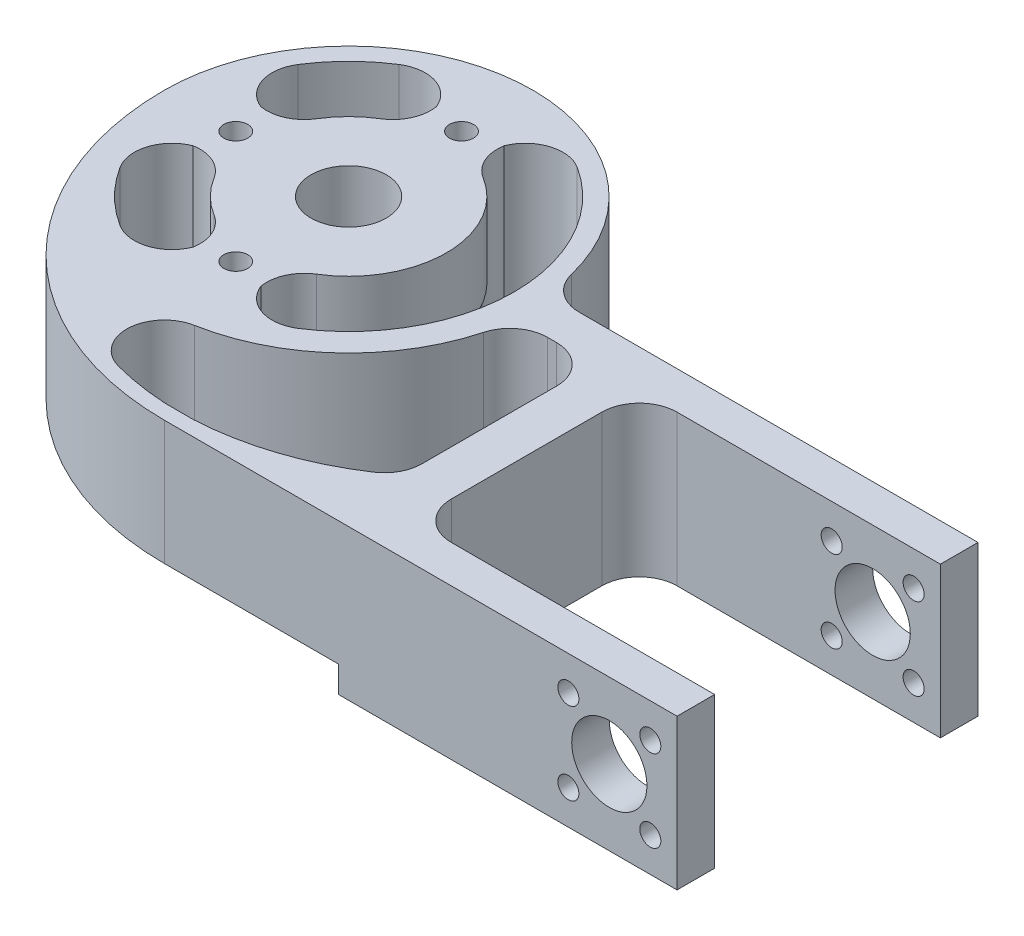
SolidWorks part; units mm, degrees
material "6061-T6 (SS)"
ref_plane "Front Plane" through (0, 0, 0) normal (0, 0, 1) x (1, 0, 0)
ref_plane "Top Plane" through (0, 0, 0) normal (0, 1, 0) x (1, 0, 0)
ref_plane "Right Plane" through (0, 0, 0) normal (1, 0, 0) x (0, 0, -1)
sketch "Sketch1" plane through (0, 0, 0) normal (0, 1, 0) x (1, 0, 0)
  circle A0 centre (0, 0) radius 31.0896
  dimension "D1" = 62.1792
extrude "Boss-Extrude1" add sketch "Sketch1" along normal blind 25.4
sketch "Sketch2" plane through (0, 25.4, 0) normal (0, 1, 0) x (1, 0, 0)
  line L0 (0, 0) -> (-31.0896, 0) construction
  line L1 (0, 0) -> (30.9857, 2.54) construction
  line L2 (46.5427, -48.26) -> (17.1704, -48.26)
  line L4 (46.5427, -48.26) -> (46.5427, 2.54)
  line L7 (30.9857, 2.54) -> (46.5427, 2.54)
  circle A0 centre (0, 0) radius 31.0896 construction
  arc A1 (17.1704, -48.26) -> (-31.0896, 0) centre (17.1704, 0) cw
  circle A2 centre (0, 0) radius 31.0896
  arc A3 (-31.0896, 0) -> (30.9857, 2.54) centre (0, 0) ccw
  dimension "D3" = 2.54
  dimension "D1" = 50.8
  dimension "D2" = 15.557
  dimension "D4" = 0
extrude "Boss-Extrude2" add sketch "Sketch2" against normal blind 20.955
sketch "Sketch3" plane through (0, 25.4, 0) normal (0, 1, 0) x (1, 0, 0)
  line L0 (46.5427, -0.3336) -> (46.5427, -48.26)
  line L1 (17.1704, -48.26) -> (46.5427, -48.26) construction
  line L2 (46.5427, -48.26) -> (103.6927, -48.26)
  line L3 (103.6927, -48.26) -> (103.6927, -41.91)
  line L4 (103.6927, -41.91) -> (52.8927, -41.91)
  line L5 (52.8927, -41.91) -> (52.8927, -3.81)
  line L6 (52.8927, -3.81) -> (103.6927, -3.81)
  line L7 (103.6927, -3.81) -> (103.6927, 2.54)
  line L8 (103.6927, 2.54) -> (46.5427, 2.54)
  line L9 (46.5427, -0.3336) -> (46.5427, 2.54)
  line L10 (46.5427, -48.26) -> (46.5427, 2.54) construction
  dimension "D1" = 57.15
  dimension "D2" = 38.1
  dimension "D3" = 6.35
  dimension "D4" = 6.35
extrude "Boss-Extrude3" add sketch "Sketch3" against normal up to surface (25.4 mm away) up to face at (0, 0, 31.0896)
sketch "Sketch4" plane through (0, 0, -2.54) normal (0, 0, -1) x (-1, 0, 0)
  line L0 (-103.6927, 12.7) -> (-92.2627, 12.7) construction
  line L1 (-103.6927, 0) -> (-103.6927, 25.4) construction
  line L2 (-92.2627, 12.7) -> (-99.1775, 5.7852) construction
  line L3 (-92.2627, 12.7) -> (-99.1775, 19.6148) construction
  line L4 (-92.2627, 12.7) -> (-99.1775, 5.7852) construction
  line L5 (-92.2627, 12.7) -> (-85.3479, 5.7852) construction
  line L6 (-92.2627, 12.7) -> (-85.3479, 19.6148) construction
  line L8 (-99.1775, 19.6148) -> (-103.6927, 19.6148) construction
  line L9 (-103.6927, 0) -> (-103.6927, 25.4) construction
  line L10 (-99.1775, 5.7852) -> (-103.6927, 5.7852) construction
  circle A0 centre (-92.2627, 12.7) radius 6.35
  circle A1 centre (-85.3479, 5.7852) radius 1.778
  circle A3 centre (-99.1775, 19.6148) radius 1.778
  circle A4 centre (-99.1775, 5.7852) radius 1.778
  circle A5 centre (-85.3479, 19.6148) radius 1.778
  dimension "D1" = 11.43
  dimension "D2" = 12.7
  dimension "D3" = 3.556
  dimension "D5" = 19.558
  dimension "D4" = 19.558
extrude "Cut-Extrude1" cut sketch "Sketch4" against normal up to surface (50.8 mm away) up to face at (53.3542, 9.5779, 48.26)
fillet "Fillet8" radius 6.35 1 edges at (30.9857, 14.9225, -2.54)
fillet "Fillet9" radius 6.35 1 edges at (52.8927, 12.7, 41.91)
fillet "Fillet10" radius 6.35 1 edges at (52.8927, 12.7, 3.81)
sketch "Sketch11" plane through (0, 4.445, 0) normal (0, -1, 0) x (-1, 0, 0)
  line L0 (-46.5427, -48.26) -> (-46.5427, 2.54)
  line L1 (-103.6927, -3.81) -> (-32.1601, -3.81)
  line L2 (-103.6927, -45.72) -> (-14.7927, -45.72)
  line L3 (-18.1864, 0) -> (-32.385, 0) construction
  line L4 (-45.2727, -3.81) -> (-45.2727, -32.8893)
  line L5 (-103.6927, -41.91) -> (-103.6927, -48.26) construction
  circle A0 centre (0, 0) radius 32.385
  arc A1 (-45.2727, -32.8893) -> (-42.4256, -38.1857) centre (-38.9227, -32.8893) ccw
  arc A2 (-17.1704, -48.26) -> (31.0896, 0) centre (-17.1704, 0) ccw construction
  arc A3 (-42.4256, -38.1857) -> (21.9087, -23.8495) centre (-17.1704, 0) ccw
  dimension "D1" = 64.77
  dimension "D3" = 88.9
  dimension "D2" = 14.1986
  dimension "D5" = 6.35
  dimension "D4" = 1.27
  dimension "D6" = 2.54
sketch "Sketch12" plane through (0, 0, 0) normal (0, -1, 0) x (1, 0, 0)
  line L0 (0, 0) -> (0, -19.05) construction
  line L1 (0, 0) -> (0, 19.05) construction
  line L2 (0, 0) -> (-19.05, 0) construction
  line L3 (0, 0) -> (19.05, 0) construction
  circle A0 centre (0, 19.05) radius 2.0193
  circle A1 centre (-19.05, 0) radius 2.0193
  circle A2 centre (0, -19.05) radius 2.0193
  dimension "D1" = 4.0386
  dimension "D2" = 19.05
extrude "Cut-Extrude7" cut sketch "Sketch12" against normal up to surface (25.4 mm away) up to face at (56.2464, 25.4, 17.0919)
extrude "Cut-Extrude8" cut sketch "Sketch11" against normal through all contours L0 A3 L2 A0 L1 region at (24.1557, 4.445, 29.3093)
sketch "Sketch14" plane through (0, 0, 0) normal (0, -1, 0) x (1, 0, 0)
  line L0 (0, 0) -> (-10.414, -10.414) construction
  line L1 (-10.414, -10.414) -> (10.414, -10.414)
  line L2 (-10.414, -10.414) -> (-10.414, 10.414)
  line L3 (-10.414, 10.414) -> (10.414, 10.414)
  line L4 (10.414, -10.414) -> (10.414, 10.414)
  line L5 (0, 0) -> (10.414, 10.414) construction
  line L6 (-10.414, 10.414) -> (0, 0) construction
  line L7 (0, 0) -> (10.414, -10.414) construction
  arc A0 (10.414, -10.414) -> (10.414, 10.414) centre (10.414, 0) ccw
  circle A1 centre (0, 0) radius 6.35
  dimension "D1" = 12.7
  dimension "D3" = 20.828
sketch "Sketch13" plane through (0, 0, 0) normal (0, -1, 0) x (1, 0, 0)
  line L0 (0, 0) -> (7.4507, 26.9283)
  line L1 (0, 0) -> (7.4507, -26.9283)
  line L2 (0, 0) -> (-7.4507, 26.9283)
  line L3 (0, 0) -> (-26.9283, 7.4507)
  line L4 (0, 0) -> (-26.9283, -7.4507)
  line L5 (0, 0) -> (-7.4507, -26.9283)
  line L6 (0, 0) -> (26.9283, 7.4507)
  line L7 (0, 0) -> (27.166, -6.531)
  circle A0 centre (0, 0) radius 27.94
  circle A1 centre (0, 0) radius 16.51
  circle A2 centre (0, 19.05) radius 2.0193 construction
  circle A3 centre (0, -19.05) radius 2.0193 construction
  circle A4 centre (-19.05, 0) radius 2.0193 construction
  circle A5 centre (-19.05, 0) radius 2.0193 construction
  dimension "D1" = 55.88
  dimension "D2" = 33.02
  dimension "D3" = 5.08
  dimension "D4" = 5.08
  dimension "D5" = 5.08
  dimension "D6" = 5.08
  dimension "D7" = 5.08
  dimension "D8" = 5.08
  dimension "D9" = 13.9817
extrude "Cut-Extrude9" cut sketch "Sketch13" against normal through all contours A1 L2 A0 L3 | A1 L4 A0 L5 | A1 L1 A0 L7 | A1 L6 A0 L0 | L7 A0 L6 region at (15.3599, 0, 15.3599) region at (15.5716, 0, -15.051) region at (-15.3599, 0, 15.3599) region at (-15.3599, 0, -15.3599) region at (22.4702, 0, 0.382)
fillet "Fillet14" radius 6.35 12 edges at (4.4027, 12.7, 15.9122) (7.4507, 12.7, 26.9283) (-26.9283, 12.7, 7.4507) (-4.4027, 12.7, 15.9122) (-15.9122, 12.7, 4.4027) (-7.4507, 12.7, 26.9283) (-7.4507, 12.7, -26.9283) (-26.9283, 12.7, -7.4507) (-4.4027, 12.7, -15.9122) (-15.9122, 12.7, -4.4027) (7.4507, 12.7, -26.9283) (4.4027, 12.7, -15.9122)
extrude "Cut-Extrude10" cut sketch "Sketch14" against normal blind 12.7 contours L1 L4 L3 L2 | L4 A0 region at (-10.1194, 0, 0) region at (14.8338, 0, 0)
fillet "Fillet17" radius 2.54 2 edges at (13.0872, 6.35, -10.0651) (13.0872, 6.35, 10.0651)
extrude "Cut-Extrude11" cut sketch "Sketch14<3>" against normal through all contours A1 region at (0, 0, 0)
sketch "Sketch14<3>" plane through (0, 0, 0) normal (0, -1, 0) x (1, 0, 0) same geometry as "Sketch14"
fillet "Fillet18" radius 3.556 2 edges at (-10.414, 6.35, 10.414) (-10.414, 6.35, -10.414)
fillet "Fillet19" radius 6.35 2 edges at (45.2727, 14.9225, 3.81) (32.1601, 14.9225, 3.81)
fillet "Fillet20" radius 6.35 1 edges at (-21.9087, 14.9225, 23.8495)
